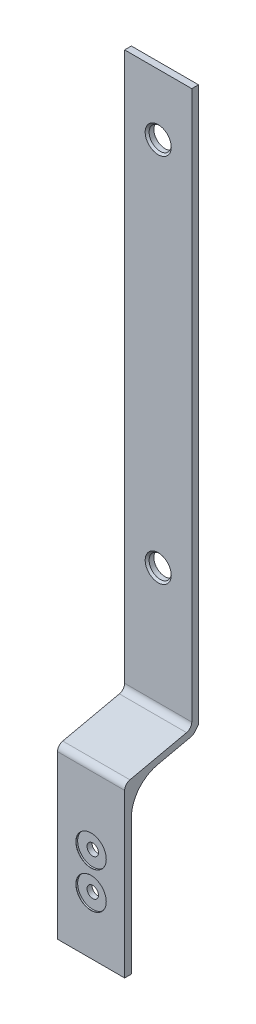
SolidWorks part; units mm, degrees
ref_plane "Piano frontale" through (0, 0, 0) normal (0, 0, 1) x (1, 0, 0)
ref_plane "Piano superiore" through (0, 0, 0) normal (0, 1, 0) x (1, 0, 0)
ref_plane "Piano destro" through (0, 0, 0) normal (1, 0, 0) x (0, 0, -1)
sketch "Schizzo1" plane through (0, 0, 0) normal (0, 0, 1) x (1, 0, 0)
  line L1 (10, 0) -> (-10, 0)
  line L2 (10, 0) -> (10, 165)
  line L3 (10, 165) -> (-10, 165)
  line L4 (-10, 0) -> (-10, 165)
  dimension "D1" = 20
  dimension "D2" = 165
ref_plane "Piano1" through (0, 0, 20) normal (0, 0, 1) x (1, 0, 0)
sketch "Schizzo4" plane through (0, 0, 20) normal (0, 0, 1) x (1, 0, 0)
  line L1 (10, -4.4276) -> (-10, -4.4276)
  line L2 (10, -4.4276) -> (10, -54.4276)
  line L3 (10, -54.4276) -> (-10, -54.4276)
  line L4 (-10, -4.4276) -> (-10, -54.4276)
  dimension "D1" = 20
  dimension "D2" = 4.4276
  dimension "D3" = 50
sketch "Schizzo5" plane through (0, 0, 0) normal (1, 0, 0) x (0, 0, -1)
  line L0 (-20, -4.4276) -> (0, 0)
  line L1 (-20, -4.4276) -> (-20, -54.4276) construction
  dimension "D1" = 20.4842
extrude "Estrusione-Sottile1" add sketch "Schizzo5" against normal mid plane 20 thin
extrude "Estrusione-Estrusione1" add sketch "Schizzo4" against normal blind 2
extrude "Estrusione-Estrusione2" add sketch "Schizzo1" against normal blind 2 separate body contours L4 L3 L2 L1
fillet "Raccordo2" radius 10 1 edges at (0, -6.0333, 18)
fillet "Raccordo8" radius 2 1 edges at (0, -4.4276, 20)
loft "Loft3" add section face at (0, 0, -1) section face at (0, -0.9764, -0.2161)
fillet "Raccordo13" radius 2 1 edges
fillet "Raccordo14" radius 2 1 edges
hole_wizard "Foro filettato G1/16-2" positions "Schizzo10" profile "Schizzo11" tap size "G1/16" standard "GB" end condition through all
sketch "Schizzo10" plane through (0, 0, 0) normal (0, 0, 1) x (1, 0, 0)
  point P0 (0, 146.8297)
  point P2 (0, 36.4098)
sketch "Schizzo11" plane through (0, 146.8297, 0) normal (1, 0, 0) x (0, -1, 0)
  line L0 (0, 0) -> (0, 2.005)
  line L1 (0, 2.005) -> (3.3, 2.005)
  line L2 (3.3, 2.005) -> (3.3, 0.5865)
  line L3 (3.3, 0.5865) -> (3.8865, 0)
  line L5 (3.8865, 0) -> (0, 0)
  line L6 (-3.3, 0.5865) -> (-3.8865, 0) construction
  line L11 (0, -6.35) -> (0, 107.95) construction
  dimension "Thru Tap Drill Dia." = 6.6
  dimension "Thru Tap Drill Depth" = 2.005
  dimension "Near C'Sink Dia." = 7.773
  dimension "Near C'Sink Angle" = 90
cosmetic thread "Filettatura del foro3" parameters "D2"=7.723
cosmetic thread "Filettatura del foro4" parameters "D2"=7.723
sketch "Schizzo23" plane through (0, 0, 18) normal (0, 0, -1) x (-1, 0, 0)
  line L0 (0, -14.0616) -> (0, -26.5302) construction
  line L2 (10, -14.0616) -> (-10, -14.0616) construction
  line L3 (0, -26.5302) -> (0, -37.4802) construction
  line L4 (-27.5, -21.0302) -> (103.7, -21.0302) construction
  dimension "D1" = 10.95
  dimension "D2" = 5.5
hole_wizard "Foro lamato per Bullone M3 a testa esagonale-4" positions "Schizzo29" profile "Schizzo27" size "M3" standard "GB" slot yes end condition through all
sketch "Schizzo29" plane through (0, 0, 20) normal (0, 0, 1) x (1, 0, 0)
  point P0 (0, -26.5302)
  point P3 (0, -37.4802)
sketch "Schizzo27" plane through (0, -26.5302, 20) normal (1, 0, 0) x (0, -1, 0)
  line L0 (0, 0) -> (0, 22.005)
  line L1 (0, 22.005) -> (1.7, 22.005)
  line L3 (1.7, 22.005) -> (1.7, 0.5)
  line L4 (4.5, 0.5) -> (1.7, 0.5)
  line L5 (4.5, 0.5) -> (4.5, 0.025)
  line L6 (4.5, 0.025) -> (4.525, 0)
  line L7 (4.525, 0) -> (0, 0)
  line L8 (-4.5, 0.025) -> (-4.525, 0) construction
  line L11 (0, -6.35) -> (0, 107.95) construction
  dimension "Thru Hole Dia." = 3.4
  dimension "Thru Hole Depth" = 22.005
  dimension "C'Bore Dia." = 9
  dimension "C'Bore Depth" = 0.5
  dimension "Near C'Sink Dia." = 9.05
  dimension "Near C'Sink Angle" = 90
